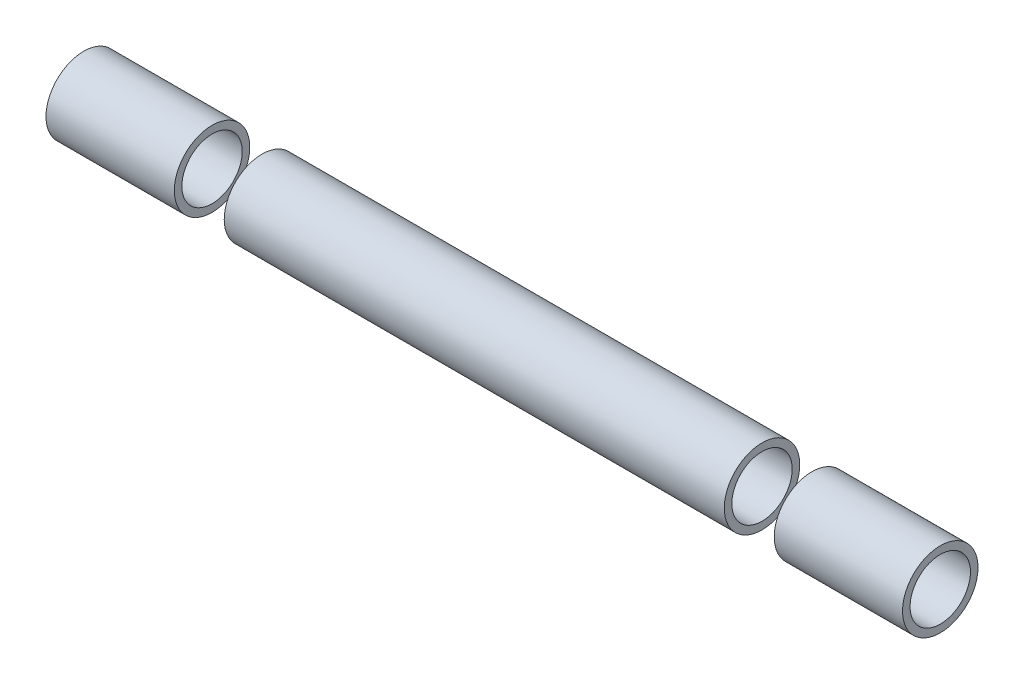
SolidWorks part; units mm, degrees
material "PC High Viscosity"
ref_plane "Front Plane" through (0, 0, 0) normal (0, 0, 1) x (1, 0, 0)
ref_plane "Top Plane" through (0, 0, 0) normal (0, 1, 0) x (1, 0, 0)
ref_plane "Right Plane" through (0, 0, 0) normal (1, 0, 0) x (0, 0, -1)
sketch "Sketch1" plane through (0, 0, 0) normal (1, 0, 0) x (0, 0, -1)
  circle A0 centre (0, 0) radius 15.875
  dimension "D1" = 31.75
extrude "Extrude-Thin1" add sketch "Sketch1" along normal mid plane 360.299 thin thin type one direction reverse wall 3.175
sketch "Sketch2" plane through (0, 0, 0) normal (0, 0, 1) x (1, 0, 0)
  line L0 (-180.1495, -15.875) -> (180.1495, -15.875) construction
  line L1 (105.1745, -15.875) -> (126.1745, -15.875)
  line L2 (105.1745, -15.875) -> (105.1745, 15.875)
  line L3 (105.1745, 15.875) -> (126.1745, 15.875)
  line L4 (126.1745, -15.875) -> (126.1745, 15.875)
  line L5 (180.1495, 15.875) -> (-180.1495, 15.875) construction
  line L6 (180.1495, -15.875) -> (180.1495, 15.875) construction
  line L7 (0, 0) -> (0, 11.1276) construction
  line L8 (-126.1745, -15.875) -> (-126.1745, 15.875)
  line L9 (-105.1745, 15.875) -> (-126.1745, 15.875)
  line L10 (-105.1745, -15.875) -> (-105.1745, 15.875)
  line L11 (-105.1745, -15.875) -> (-126.1745, -15.875)
  dimension "D1" = 53.975
  dimension "D2" = 21
extrude "Cut-Extrude1" cut sketch "Sketch2" against normal through all both and the other way through all
equation "\"D2@Sketch2\"=21mm"
